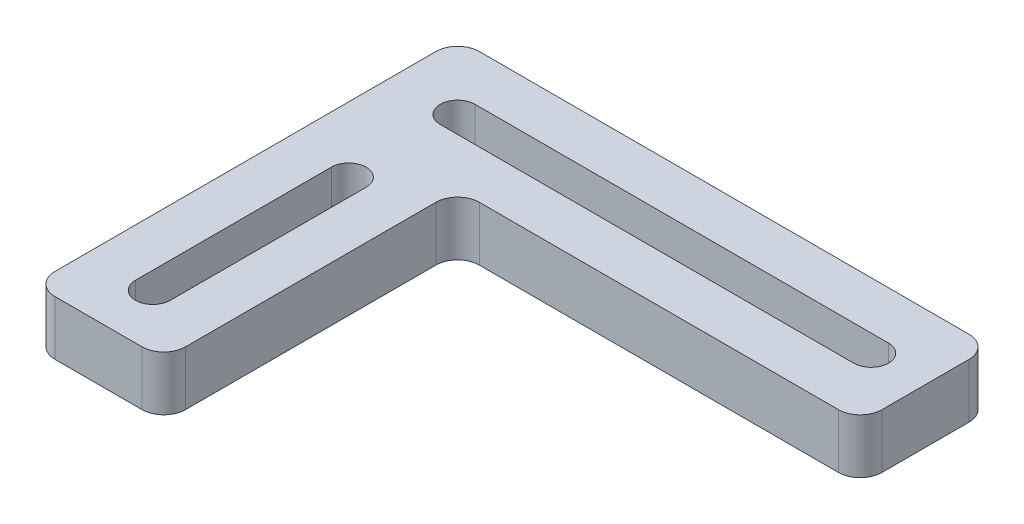
SolidWorks part; units mm, degrees
ref_plane "Front Plane" through (0, 0, 0) normal (0, 0, 1) x (1, 0, 0)
ref_plane "Top Plane" through (0, 0, 0) normal (0, 1, 0) x (1, 0, 0)
ref_plane "Right Plane" through (0, 0, 0) normal (1, 0, 0) x (0, 0, -1)
sketch "Sketch1" plane through (0, 0, 0) normal (0, 1, 0) x (1, 0, 0)
  line L0 (4, -2) -> (4, 3) construction
  line L1 (0, -2) -> (8, -2)
  line L2 (-2, 0) -> (-2, 35)
  line L3 (0, 37) -> (45, 37)
  line L4 (10, 0) -> (10, 23)
  line L5 (47, 35) -> (47, 27)
  line L6 (45, 25) -> (12, 25)
  line L7 (4, 3) -> (4, 21) construction
  line L8 (47, 31) -> (42, 31) construction
  line L9 (42, 31) -> (4, 31) construction
  line L10 (42, 29.4) -> (4, 29.4)
  line L11 (42, 32.6) -> (4, 32.6)
  line L12 (2.4, 3) -> (2.4, 21)
  line L13 (5.6, 3) -> (5.6, 21)
  arc A0 (0, -2) -> (-2, 0) centre (0, 0) cw
  arc A1 (8, -2) -> (10, 0) centre (8, 0) ccw
  arc A2 (12, 25) -> (10, 23) centre (12, 23) ccw
  arc A3 (47, 27) -> (45, 25) centre (45, 27) cw
  arc A4 (47, 35) -> (45, 37) centre (45, 35) ccw
  arc A5 (0, 37) -> (-2, 35) centre (0, 35) ccw
  arc A6 (2.4, 3) -> (5.6, 3) centre (4, 3) ccw
  arc A7 (5.6, 21) -> (2.4, 21) centre (4, 21) ccw
  arc A8 (42, 29.4) -> (42, 32.6) centre (42, 31) ccw
  arc A9 (4, 32.6) -> (4, 29.4) centre (4, 31) ccw
  point P6 (4, 12)
  point P27 (23, 31)
  dimension "D1" = 2
  dimension "D6" = 3.2
  dimension "D7" = 18
  dimension "D2" = 8
  dimension "D3" = 45
  dimension "D4" = 8
  dimension "D5" = 35
  dimension "D8" = 5
  dimension "D9" = 3.2
  dimension "D10" = 5
  dimension "D11" = 38
extrude "Boss-Extrude1" add sketch "Sketch1" along normal blind 5 contours L3 A5 L2 A0 L1 A1 L4 A2 L6 A3 L5 A4 A9 L11 A8 L10 region at (-0.9714, 0, 0.9714)
